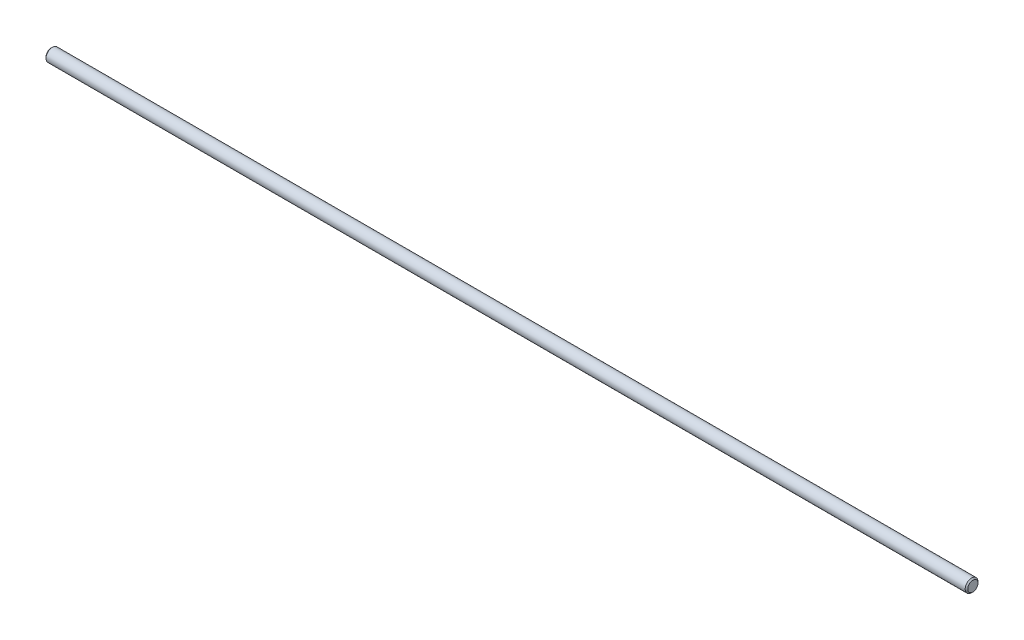
SolidWorks part; units mm, degrees
material "AISI 4130 Steel, normalized at 870C"
ref_plane "Front" through (0, 0, 0) normal (0, 0, 1) x (1, 0, 0)
ref_plane "Top" through (0, 0, 0) normal (0, 1, 0) x (1, 0, 0)
ref_plane "Right" through (0, 0, 0) normal (1, 0, 0) x (0, 0, -1)
sketch "Sketch1" plane through (0, 0, 0) normal (0, 0, 1) x (1, 0, 0)
  line L0 (-228.6, 0) -> (228.6, 0) construction
  line L1 (228.6, 3.175) -> (228.6, -3.175) construction
  line L2 (-228.6, 3.175) -> (-228.6, -3.175) construction
  dimension "Length" = 457.2
  dimension "Diameter" = 6.35
sketch "Sketch2" plane through (0, 0, 0) normal (1, 0, 0) x (0, 0, -1)
  circle A0 centre (0, 0) radius 3.175
extrude "Extrude1" add sketch "Sketch2" against normal up to vertex (228.6 mm away) and the other way up to vertex (228.6 mm away) up to point (-228.6, 3.175, 0) other way up to point (228.6, 3.175, 0)
chamfer "Chamfer1" distance 0.635 angle 45 2 edges at (228.6, 0, -3.175) (-228.6, 0, -3.175)
equation "\"D1@Chamfer1\" = \"Diameter@Sketch1\"*.1"
